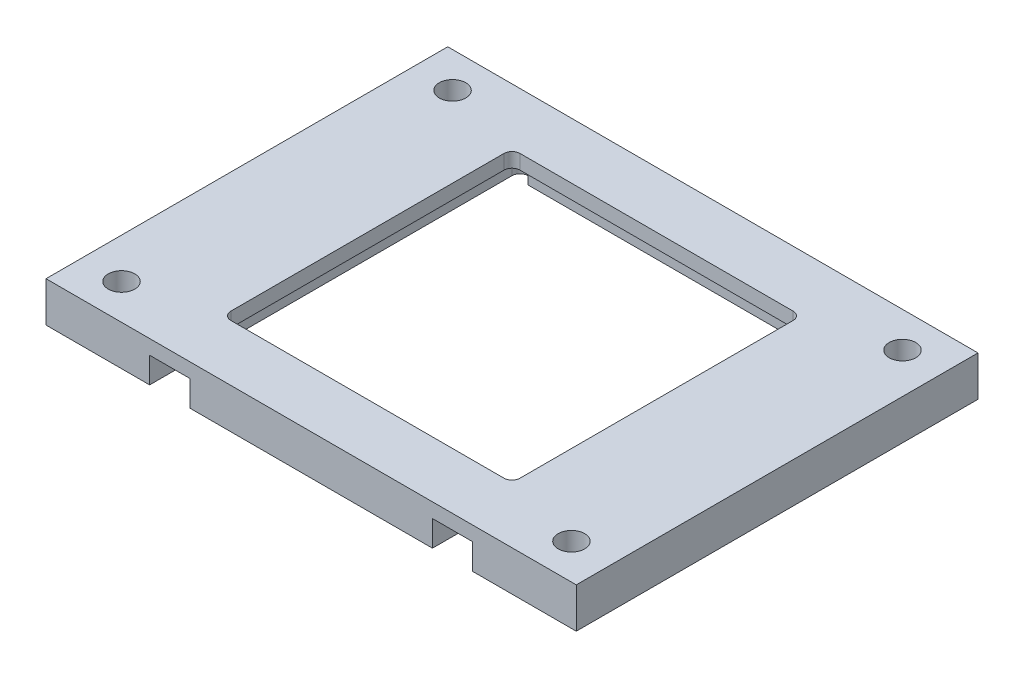
SolidWorks part; units mm, degrees
ref_plane "Front Plane" through (0, 0, 0) normal (0, 0, 1) x (1, 0, 0)
ref_plane "Top Plane" through (0, 0, 0) normal (0, 1, 0) x (1, 0, 0)
ref_plane "Right Plane" through (0, 0, 0) normal (1, 0, 0) x (0, 0, -1)
sketch "Sketch1" plane through (0, 0, 0) normal (0, 1, 0) x (1, 0, 0)
  line L0 (20.1, -20.1) -> (20.1, 21.1)
  line L1 (-20.1, -20.1) -> (20.1, -20.1)
  line L3 (-18.1, 20.1) -> (18.1, 20.1)
  line L5 (-20.1, 21.1) -> (-20.1, -20.1)
  line L7 (-33, -25) -> (33, -25)
  line L8 (-33, -25) -> (-33, 25)
  line L9 (-33, 25) -> (33, 25)
  line L10 (33, -25) -> (33, 25)
  line L11 (-33, -25) -> (33, 25) construction
  line L12 (-33, 25) -> (33, -25) construction
  line L15 (-20.1, 21.1) -> (-18.1, 21.1)
  line L16 (-18.1, 20.1) -> (-18.1, 21.1)
  line L19 (20.1, 21.1) -> (18.1, 21.1)
  line L20 (18.1, 20.1) -> (18.1, 21.1)
  circle A0 centre (-28, 20.6) radius 1.65
  circle A1 centre (28, 20.6) radius 1.65
  circle A2 centre (-28, -20.6) radius 1.65
  circle A3 centre (28, -20.6) radius 1.65
  point P0 (0, 0)
  point P15 (0, 0)
  dimension "D3" = 20.6
  dimension "D4" = 20.6
  dimension "D5" = 20.6
  dimension "D6" = 20.6
  dimension "D7" = 28
  dimension "D10" = 28
  dimension "D11" = 3.3
  dimension "D14" = 2
  dimension "D2" = 40.2
  dimension "D8" = 28
  dimension "D9" = 28
  dimension "D12" = 66
  dimension "D13" = 50
  dimension "D15" = 1
  dimension "D16" = 2
  dimension "D17" = 1
  dimension "D18" = 20.1
  dimension "D19" = 40.2
  dimension "D20" = 20.1
extrude "Boss-Extrude1" add sketch "Sketch1" along normal blind 5
sketch "Sketch2" plane through (0, 5, 0) normal (0, 1, 0) x (1, 0, 0)
  line L12 (-18, -18) -> (18, -18)
  line L13 (18, -18) -> (18, 18)
  line L14 (-18, 18) -> (-18, -18)
  line L15 (18, 18) -> (-18, 18)
  line L54 (-20.1, 21.1) -> (-20.1, -20.1)
  line L55 (-20.1, -20.1) -> (20.1, -20.1)
  line L56 (20.1, -20.1) -> (20.1, 21.1)
  line L57 (20.1, 21.1) -> (18.1, 21.1)
  line L58 (18.1, 21.1) -> (18.1, 20.1)
  line L59 (18.1, 20.1) -> (-18.1, 20.1)
  line L60 (-18.1, 20.1) -> (-18.1, 21.1)
  line L61 (-18.1, 21.1) -> (-20.1, 21.1)
  line L62 (-20.1, 21.1) -> (-20.1, -20.1)
  line L63 (-20.1, -20.1) -> (20.1, -20.1)
  line L64 (20.1, -20.1) -> (20.1, 21.1)
  line L65 (20.1, 21.1) -> (18.1, 21.1)
  line L66 (18.1, 21.1) -> (18.1, 20.1)
  line L67 (18.1, 20.1) -> (-18.1, 20.1)
  line L68 (-18.1, 20.1) -> (-18.1, 21.1)
  line L69 (-18.1, 21.1) -> (-20.1, 21.1)
  dimension "D1" = 36
  dimension "D3" = 36
  dimension "D4" = 18
  dimension "D5" = 18
  dimension "D6" = 36
  dimension "D7" = 36
  dimension "D2" = 0
extrude "Boss-Extrude2" add sketch "Sketch2" against normal blind 1.8
sketch "Sketch3" plane through (0, 0, 25) normal (0, 0, 1) x (1, 0, 0)
  line L0 (-33, 0) -> (33, 0) construction
  line L1 (-20.1, 0) -> (-15.1, 0)
  line L3 (-20.1, 3.2) -> (-15.1, 3.2)
  line L4 (-15.1, 0) -> (-15.1, 3.2)
  line L5 (20.1, 0) -> (20.1, 3.2)
  line L6 (20.1, 0) -> (15.1, 0)
  line L8 (20.1, 3.2) -> (15.1, 3.2)
  line L9 (15.1, 0) -> (15.1, 3.2)
  line L10 (-20.1, 0) -> (-20.1, 3.2)
  dimension "D1" = 5
  dimension "D2" = 5
  dimension "D3" = 0
  dimension "D4" = 0
  dimension "D5" = 3.2
  dimension "D6" = 3.2
extrude "Cut-Extrude1" cut sketch "Sketch3" against normal up to next
fillet "Fillet1" radius 1 8 edges at (-18, 4.1, 18) (18, 4.1, 18) (18, 4.1, -18) (-18, 4.1, -18) (-20.1, 1.6, -21.1) (-18.1, 1.6, -21.1) (18.1, 1.6, -21.1) (20.1, 1.6, -21.1)
sketch "Sketch4" plane through (0, 0, 0) normal (0, 1, 0) x (1, 0, 0)
